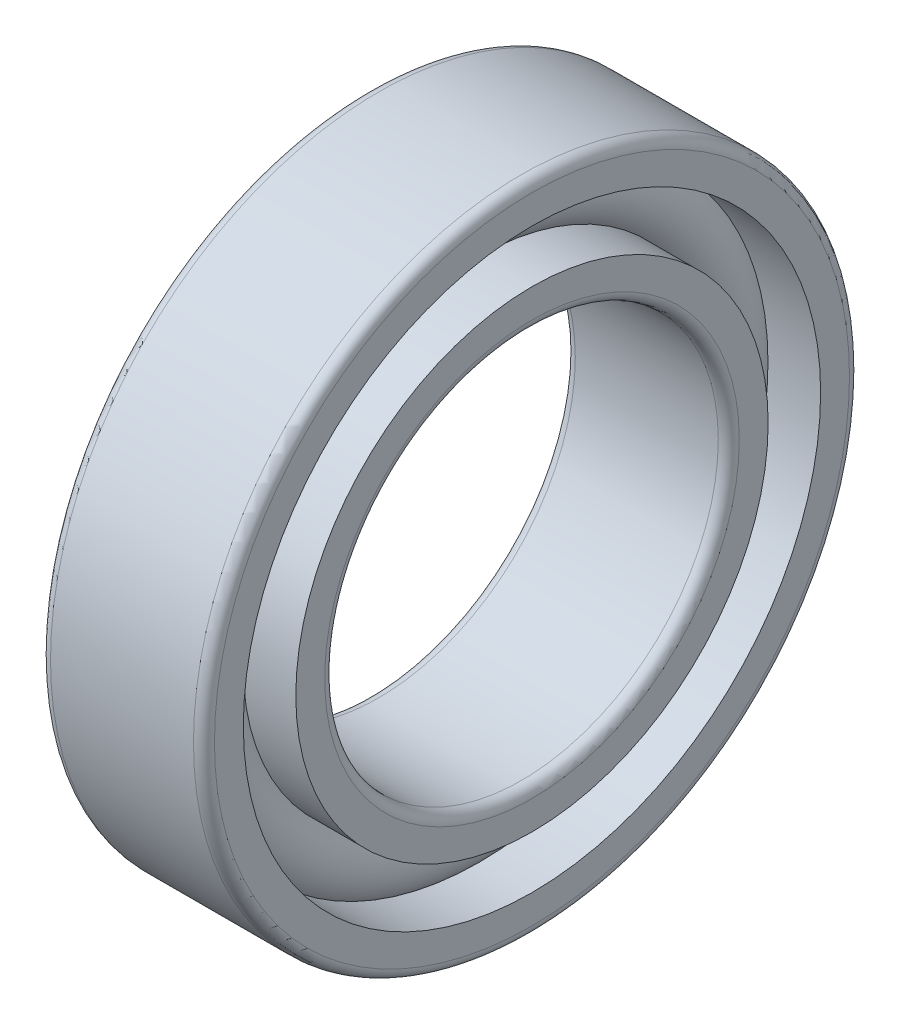
SolidWorks part; units mm, degrees
ref_plane "Plane1" through (0, 0, 0) normal (0, 0, 1) x (1, 0, 0)
ref_plane "Plane2" through (0, 0, 0) normal (0, 1, 0) x (1, 0, 0)
ref_plane "Plane3" through (0, 0, 0) normal (1, 0, 0) x (0, 0, -1)
other "Configuration Table"
sketch "Clipboard" plane through (0, 0, 0) normal (0, 0, 1) x (1, 0, 0)
  line L0 (-10, 0) -> (10, 0) construction
  line L1 (0, 0) -> (22.3471, -0.7804)
  line L2 (0, 0) -> (6.3461, 0.2216)
  line L3 (0, 0) -> (22.3471, -0.7804)
  line L4 (0, 0) -> (-22.3573, -0.3902)
  dimension "BallCLRad" = 6.35
sketch "CagSpiSke" plane through (0, 0, 0) normal (0, 0, 1) x (1, 0, 0)
  line L0 (0.0952, 6.1913) -> (0.0953, 6.5087)
  line L1 (0.0953, 6.5087) -> (-0.0953, 6.5087)
  line L2 (-0.0953, 6.5087) -> (-0.0952, 6.1913)
  line L3 (-0.0952, 6.1913) -> (0.0952, 6.1913)
  line L4 (-20.6375, 0) -> (20.6375, 0) construction
  line L5 (0, 0) -> (0, 23.7692) construction
  dimension "OD" = 13.0175
  dimension "ID" = 12.3825
revolve "CageSpine" add sketch "CagSpiSke" angle 0.001 about L4 reverse direction yes
ref_axis "Axis1" through (-50, 0, 0) along (1, 0, 0)
sketch "CagBalSke" plane through (0, 0, 0) normal (0, 0, 1) x (1, 0, 0)
  line L0 (-1.0477, 6.35) -> (1.0477, 6.35)
  line L1 (-1.905, 6.35) -> (1.905, 6.35) construction
  line L2 (-10, 0) -> (10, 0) construction
  line L3 (0, 0) -> (0, 24) construction
  arc A0 (1.0477, 6.35) -> (-1.0477, 6.35) centre (0, 6.35) cw
  dimension "BallCLRad" = 6.35
revolve "CageBall" [suppressed] add sketch "CagBalSke" angle 360 about L1 reverse direction yes
pattern_circular "CageBalls" [suppressed] count 2 every 180 about axis through (-50, 0, 0) along (1, 0, 0)
sketch "CagTrmODSke" plane through (0, 0, 0) normal (0, 0, 1) x (1, 0, 0)
  line L0 (1.0731, 6.5087) -> (1.0732, 7.4231)
  line L1 (1.0732, 7.4231) -> (-1.0732, 7.4231)
  line L2 (-1.0732, 7.4231) -> (-1.0731, 6.5087)
  line L3 (-1.0731, 6.5087) -> (1.0731, 6.5087)
  line L4 (-20.6375, 0) -> (20.6375, 0) construction
  line L5 (0, 0) -> (0, 25) construction
  dimension "Width" = 2.1463
  dimension "ID" = 13.0175
  dimension "OD" = 14.8463
revolve "CageTrimOD" [suppressed] cut sketch "CagTrmODSke" angle 360 about L4 reverse direction yes
sketch "CagTrmIDSke" plane through (0, 0, 0) normal (0, 0, 1) x (1, 0, 0)
  line L0 (1.0732, 5.3276) -> (1.0732, 6.1913)
  line L1 (1.0732, 6.1913) -> (-1.0732, 6.1913)
  line L2 (-1.0732, 6.1913) -> (-1.0732, 5.3276)
  line L3 (-1.0732, 5.3276) -> (1.0732, 5.3276)
  line L4 (-20.6375, 0) -> (20.6375, 0) construction
  line L5 (0, 0) -> (0, 25) construction
  dimension "Width" = 2.1463
  dimension "ID" = 10.6553
  dimension "OD" = 12.3825
revolve "CageTrimID" [suppressed] cut sketch "CagTrmIDSke" angle 360 about L4 reverse direction yes
sketch "BalSimSke" plane through (0, 0, 0) normal (0, 0, 1) x (1, 0, 0)
  line L0 (-10, 0) -> (10, 0) construction
  line L1 (-10, 6.35) -> (10, 6.35) construction
  line L2 (0, 0) -> (0, 23) construction
  circle A0 centre (0, 6.35) radius 0.9525
  dimension "BallCLRad" = 6.35
  dimension "Ball_diameter" = 1.905
revolve "BallsSimplified" add sketch "BalSimSke" angle 360 about L0
sketch "BalDetSke" plane through (0, 0, 0) normal (0, 0, 1) x (1, 0, 0)
  line L0 (-0.9525, 6.35) -> (0.9525, 6.35)
  line L1 (-1.905, 6.35) -> (1.905, 6.35) construction
  line L2 (0, 0) -> (0, 25) construction
  arc A0 (0.9525, 6.35) -> (-0.9525, 6.35) centre (0, 6.35) cw
  dimension "BallCLRad" = 6.35
  dimension "Ball_diameter" = 1.905
revolve "BallDetailed" [suppressed] add sketch "BalDetSke" angle 360 about L1 reverse direction yes
sketch "InnRacSke" plane through (0, 0, 0) normal (0, 0, 1) x (1, 0, 0)
  line L0 (-0.6501, 5.715) -> (-1.9837, 5.715)
  line L1 (-1.9837, 5.715) -> (-1.9837, 5.0165)
  line L2 (-1.7297, 4.7625) -> (1.7297, 4.7625)
  line L3 (1.9837, 5.0165) -> (1.9837, 5.715)
  line L4 (1.9837, 5.715) -> (0.7009, 5.715)
  line L5 (-20.6375, 0) -> (20.6375, 0) construction
  line L6 (0, 0) -> (0, 30) construction
  arc A0 (-1.9837, 5.0165) -> (-1.7297, 4.7625) centre (-1.7297, 5.0165) ccw
  arc A1 (1.7297, 4.7625) -> (1.9837, 5.0165) centre (1.7297, 5.0165) ccw
  arc A2 (0.7009, 5.715) -> (-0.6501, 5.715) centre (0.0254, 6.35) cw
  dimension "BallCLRad" = 6.35
  dimension "Fillet_radius" = 0.254
  dimension "Ball_diameter" = 1.8542
  dimension "ID" = 9.525
  dimension "OD" = 11.43
  dimension "Width" = 3.9675
revolve "InnerRace" add sketch "InnRacSke" angle 360 about L5 reverse direction yes
sketch "OutRacSke" plane through (0, 0, 0) normal (0, 0, 1) x (1, 0, 0)
  line L0 (-0.6755, 6.985) -> (-1.9837, 6.985)
  line L1 (-1.9837, 6.985) -> (-1.9837, 7.6835)
  line L2 (-1.7297, 7.9375) -> (1.7297, 7.9375)
  line L3 (1.9837, 7.6835) -> (1.9837, 6.985)
  line L4 (1.9837, 6.985) -> (0.6755, 6.985)
  line L5 (-20.6375, 0) -> (20.6375, 0) construction
  line L6 (0, 0) -> (0, 30) construction
  arc A0 (-1.9837, 7.6835) -> (-1.7297, 7.9375) centre (-1.7297, 7.6835) cw
  arc A1 (1.7297, 7.9375) -> (1.9837, 7.6835) centre (1.7297, 7.6835) cw
  arc A2 (0.6755, 6.985) -> (-0.6755, 6.985) centre (0, 6.35) ccw
  dimension "BallCLRad" = 6.35
  dimension "Fillet_radius" = 0.254
  dimension "Ball_diameter" = 1.8542
  dimension "Width" = 3.9675
revolve "OuterRace" add sketch "OutRacSke" angle 360 about L5 reverse direction yes
pattern_circular "BallsDetailed" [suppressed] count 2 every 180 about axis through (-50, 0, 0) along (1, 0, 0)
equation "\"BallCLRad@Clipboard\" = ( \"OD@OutRacSke\" + \"ID@InnRacSke\" ) / 4"
equation "\"BallCLRad@BalSimSke\" = \"BallCLRad@Clipboard\""
equation "\"BallCLRad@BalDetSke\" = \"BallCLRad@Clipboard\""
equation "\"BallCLRad@InnRacSke\" = \"BallCLRad@Clipboard\""
equation "\"BallCLRad@OutRacSke\" = \"BallCLRad@Clipboard\""
equation "\"Ball_diameter@InnRacSke\" = \"Ball_diameter@BalDetSke\" - 0.002"
equation "\"Ball_diameter@OutRacSke\" = \"Ball_diameter@BalDetSke\" - 0.002"
equation "\"Ball_diameter@BalSimSke\" = \"Ball_diameter@BalDetSke\""
equation "\"Width@OutRacSke\" = \"Width@InnRacSke\""
equation "\"Fillet_radius@OutRacSke\" = \"Fillet_radius@InnRacSke\""
equation "\"Max_count@Clipboard\" = int( 3.14159265 / atn(( \"Ball_diameter@BalDetSke\" / 2) / sqr( \"BallCLRad@Clipboard\"  *  \"BallCLRad@Clipboard\" - ( \"Ball_diameter@BalDetSke\" / 2) *  ( \"Ball_diameter@BalDetSke\" / 2))))"
equation "\"Max_count@Clipboard\" = ((sgn( \"Max_count@Clipboard\" - \"Count@Clipboard\" )-1)*( \"Max_count@Clipboard\" - \"Count@Clipboard\" ))/-2+ \"Count@Clipboard\""
equation "\"Count@BallsDetailed\" = int( \"Show_count@Clipboard\" ) "
equation "\"Count@BallsDetailed\" = ((sgn( \"Count@BallsDetailed\" - \"Max_count@Clipboard\" )-1)*( \"Count@BallsDetailed\" - \"Max_count@Clipboard\" ))/-2+ \"Max_count@Clipboard\""
equation "\"Count@BallsDetailed\" = ((sgn( \"Count@BallsDetailed\" - \"Min_count@Clipboard\" )+1)*( \"Count@BallsDetailed\" - \"Min_count@Clipboard\"))/2 +\"Min_count@Clipboard\""
equation "\"Angle@BallsDetailed\" = 360.0 / \"Max_count@Clipboard\""
equation "\"BallCLRad@CagBalSke\" = \"BallCLRad@Clipboard\""
equation "\"Count@CageBalls\" = \"Count@BallsDetailed\""
equation "\"Angle@CageBalls\" = \"Angle@BallsDetailed\""
equation "\"Angle@CageSpine\" =  \"Angle@CageBalls\" * ( \"Count@CageBalls\" -1 + int( \"Count@CageBalls\" / \"Max_count@Clipboard\" ) )  + 0.001 -  int( \"Count@CageBalls\" / \"Max_count@Clipboard\" ) * 0.001"
equation "\"Angle@CageSpine\" =  \"Angle@CageSpine\" * int( \"Min_count@Clipboard\" / 2) + int(1 / \"Min_count@Clipboard\")  * 0.001"
equation "\"CageWallOD@CagBalSke\" =  \"Ball_diameter@BalDetSke\" * 1.1"
equation "\"Thickness@CagSpiSke\" =  \"Ball_diameter@BalDetSke\" * 0.1"
equation "\"OD@CagTrmODSke\" = \"BallCLRad@Clipboard\" * 2 + \"CageWallOD@CagBalSke\" + 0.002"
equation "\"ID@CagTrmODSke\" = \"BallCLRad@Clipboard\" * 2 + \"Ball_diameter@BalDetSke\" / 6"
equation "\"OD@CagTrmIDSke\" = \"BallCLRad@Clipboard\" * 2 - \"Ball_diameter@BalDetSke\" / 6"
equation "\"ID@CagTrmIDSke\" = \"BallCLRad@Clipboard\" * 2 - \"CageWallOD@CagBalSke\" + 0.002"
equation "\"OD@CagSpiSke\" = \"ID@CagTrmODSke\""
equation "\"ID@CagSpiSke\" = \"OD@CagTrmIDSke\""
equation "\"Width@CagTrmODSke\" = \"CageWallOD@CagBalSke\" + 0.002"
equation "\"Width@CagTrmIDSke\" = \"CageWallOD@CagBalSke\" + 0.002"
